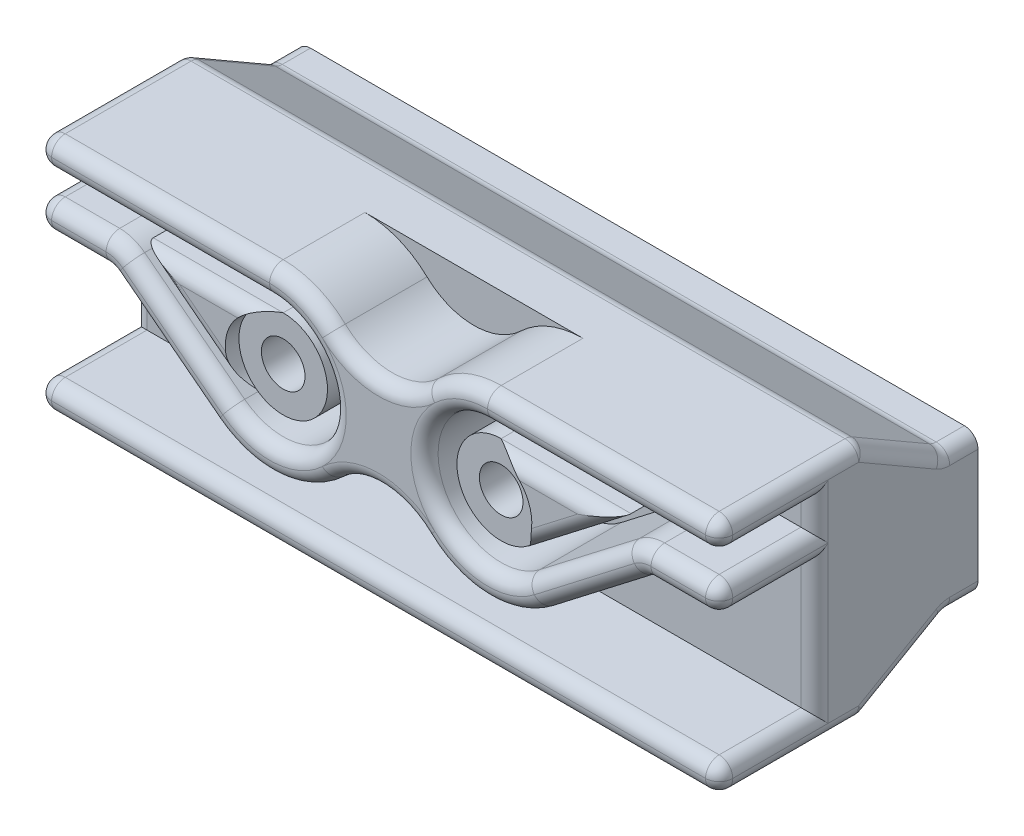
SolidWorks part; units mm, degrees
note: The reader was unsure of these and kept them because the rebuilt part matched: shared geometry of "Эскиз1<3>", "Эскиз1<4>".
ref_plane "Спереди" through (0, 0, 0) normal (0, 0, 1) x (1, 0, 0)
ref_plane "Сверху" through (0, 0, 0) normal (0, 1, 0) x (1, 0, 0)
ref_plane "Справа" through (0, 0, 0) normal (1, 0, 0) x (0, 0, -1)
sketch "Эскиз1" plane through (0, 0, 0) normal (0, 0, 1) x (1, 0, 0)
  line L0 (-25, 6.74) -> (25, 6.74) construction
  line L1 (25, -6.74) -> (-25, -6.74)
  line L2 (-25, 5.36) -> (25, 5.36) construction
  line L3 (-25, -8.74) -> (25, -8.74)
  line L4 (-25, -8.74) -> (-25, 8.74)
  line L5 (-25, 8.74) -> (25, 8.74)
  line L6 (25, -8.74) -> (25, 8.74)
  line L7 (-25, -8.74) -> (25, 8.74) construction
  line L8 (-25, 8.74) -> (25, -8.74) construction
  line L9 (25, 4.73) -> (-25, 4.73) construction
  line L10 (-59.4659, 0) -> (63.741, 0) construction
  line L11 (0, 12.1475) -> (0, -15.9359) construction
  line L12 (8, 5.36) -> (17.5347, 5.36)
  line L13 (17.5347, 5.36) -> (9.985, -0.4634)
  line L14 (20, 4.73) -> (25, 4.73)
  line L15 (10.8278, -1.5561) -> (18.1677, 4.1054)
  line L16 (8, 6.74) -> (25, 6.74)
  line L17 (25, 2.73) -> (20, 2.73)
  line L18 (19.3892, 2.5218) -> (12.0493, -3.1397)
  line L19 (-20, 4.73) -> (-25, 4.73)
  line L20 (-25, 2.73) -> (-20, 2.73)
  line L21 (-17.5347, 5.36) -> (-9.985, -0.4634)
  line L22 (-10.8278, -1.5561) -> (-18.1677, 4.1054)
  line L23 (-19.3892, 2.5218) -> (-12.0493, -3.1397)
  line L24 (-8, 5.36) -> (-17.5347, 5.36)
  line L25 (-8, 6.74) -> (-25, 6.74)
  arc A0 (8, 5.36) -> (9.985, -0.4634) centre (8, 2.11) ccw
  arc A1 (20, 4.73) -> (18.1677, 4.1054) centre (20, 1.73) ccw
  arc A2 (10.8278, -1.5561) -> (8, 6.74) centre (8, 2.11) cw
  circle A3 centre (8, 2.11) radius 1.6
  arc A4 (8, 8.74) -> (3.4394, 6.9222) centre (8, 2.11) ccw
  arc A5 (3.4394, 6.9222) -> (-3.4394, 6.9222) centre (0, 10.5514) cw
  arc A6 (20, 2.73) -> (19.3892, 2.5218) centre (20, 1.73) ccw
  arc A7 (12.0493, -3.1397) -> (3.4394, -2.7022) centre (8, 2.11) cw
  arc A8 (-3.4394, -2.7022) -> (3.4394, -2.7022) centre (0, -6.3314) cw
  arc A9 (-20, 2.73) -> (-19.3892, 2.5218) centre (-20, 1.73) cw
  arc A10 (-20, 4.73) -> (-18.1677, 4.1054) centre (-20, 1.73) cw
  arc A11 (-12.0493, -3.1397) -> (-3.4394, -2.7022) centre (-8, 2.11) ccw
  circle A12 centre (-8, 2.11) radius 1.6
  arc A13 (-8, 5.36) -> (-9.985, -0.4634) centre (-8, 2.11) cw
  arc A14 (-10.8278, -1.5561) -> (-8, 6.74) centre (-8, 2.11) ccw
  arc A15 (-8, 8.74) -> (-3.4394, 6.9222) centre (-8, 2.11) cw
  point P4 (0, 0)
  dimension "D8" = 3.25
  dimension "D10" = 3
  dimension "D11" = 3.2
  dimension "D12" = 5
  dimension "D1" = 50
  dimension "D2" = 17.48
  dimension "D3" = 1.38
  dimension "D4" = 2
  dimension "D5" = 0.63
  dimension "D6" = 2
  dimension "D7" = 8
  dimension "D9" = 5
  dimension "D13" = 2
extrude "Бобышка-Вытянуть1" add sketch "Эскиз1" along normal blind 12 contours L3 L6 L5 L4
extrude "Бобышка-Вытянуть2" add sketch "Эскиз1<3>" along normal blind 7 from surface at 12 contours L3 L6 L1 L4 | A15 L5 L4 L25 A14 L22 A10 L19 L20 A9 L23 A11 A8 A7 L18 A6 L17 L6 L14 A1 L15 A2 L16 A4 A5 | L13 A0 L12 | L24 L21 A13 starting at face at (0, 0, 12)
sketch "Эскиз1<3>" plane through (0, 0, 0) normal (0, 0, 1) x (1, 0, 0) same geometry as "Эскиз1"
extrude "Вырез-Вытянуть1" cut sketch "Эскиз1<4>" along normal blind 19 contours A3 | A12
sketch "Эскиз1<4>" plane through (0, 0, 0) normal (0, 0, 1) x (1, 0, 0) same geometry as "Эскиз1"
sketch "Эскиз3" plane through (0, 0, 0) normal (1, 0, 0) x (0, 0, -1)
  line L0 (0, 8.74) -> (0, 5.1849)
  line L1 (0, -8.74) -> (0, 8.74) construction
  line L2 (0, 5.1849) -> (-2.3396, 5.1849)
  line L3 (-2.3396, 5.1849) -> (-8.4971, 8.74)
  line L4 (-19, 8.74) -> (0, 8.74) construction
  line L5 (-8.4971, 8.74) -> (0, 8.74)
  line L6 (0, -8.74) -> (0, -5.1849)
  line L7 (0, -5.1849) -> (-2.3396, -5.1849)
  line L8 (-2.3396, -5.1849) -> (-8.4971, -8.74)
  line L9 (-19, -8.74) -> (0, -8.74) construction
  line L10 (-8.4971, -8.74) -> (0, -8.74)
  line L11 (-15, 20) -> (20.723, -0.6247) construction
  line L12 (-28.8206, 0) -> (28.5311, 0) construction
  line L13 (0.9724, 13.6651) -> (-1.5276, 9.3349) construction
  point P23 (-0.2776, 11.5)
  dimension "D1" = 30
  dimension "D2" = 20
  dimension "D3" = 15
  dimension "D4" = 6.5
  dimension "D5" = 5
  dimension "D6" = 17
  dimension "D7" = 4.15
extrude "Вырез-Вытянуть3" cut sketch "Эскиз3" against normal mid plane 50
fillet "Скругление1" radius 1 60 edges at (12.7673, 5.36, 19) (4.9238, 1.0614, 19) (-12.7673, 5.36, 19) (-4.9238, 1.0614, 19) (-16.5, 6.74, 19) (-3.6176, 0.6162, 19) (-14.4978, 1.2747, 19) (-19.0321, 4.5696, 19) (-16.5, 8.74, 19) (-5.5452, 8.2688, 19) (0, 5.5514, 19) (5.5452, 8.2688, 19) (-22.5, 2.73, 19) (-19.6774, 2.6765, 19) (-15.7193, -0.309, 19) (-7.6635, -4.5115, 19) (0, -1.3314, 19) (7.6635, -4.5115, 19) (15.7193, -0.309, 19) (19.6774, 2.6765, 19) (16.5, 6.74, 19) (3.6176, 0.6162, 19) (14.4978, 1.2747, 19) (19.0321, 4.5696, 19) (13.7598, 2.4483, 19) (-13.7598, 2.4483, 19) (-22.5, 4.73, 19) (16.5, 8.74, 19) (22.5, 2.73, 19) (22.5, 4.73, 19) (0, -6.74, 19) (0, -8.74, 19) (-25, -8.74, 13.7486) (-25, 8.74, 13.7486) (-25, 6.74, 15.5) (-25, 4.73, 15.5) (-25, 2.73, 15.5) (25, 8.74, 13.7486) (25, 6.74, 15.5) (25, 4.73, 15.5) (25, 2.73, 15.5) (25, -8.74, 13.7486) (-25, 5.1849, 1.1698) (25, 5.1849, 1.1698) (-25, -5.1849, 1.1698) (25, -5.1849, 1.1698) (-25, 6.9625, 5.4183) (25, 6.9625, 5.4183) (-25, -6.9625, 5.4183) (25, -6.9625, 5.4183) (0, -8.74, 8.4971) (0, -5.1849, 2.3396) (0, 8.74, 8.4971) (0, 5.1849, 2.3396)
sketch "Эскиз2" plane through (0, 0, 19) normal (0, 0, 1) x (1, 0, 0)
  circle A0 centre (-8, 2.11) radius 3.25
  circle A1 centre (8, 2.11) radius 3.25
  dimension "D1" = 6.5
extrude "Вырез-Вытянуть2" cut sketch "Эскиз2" against normal blind 1
